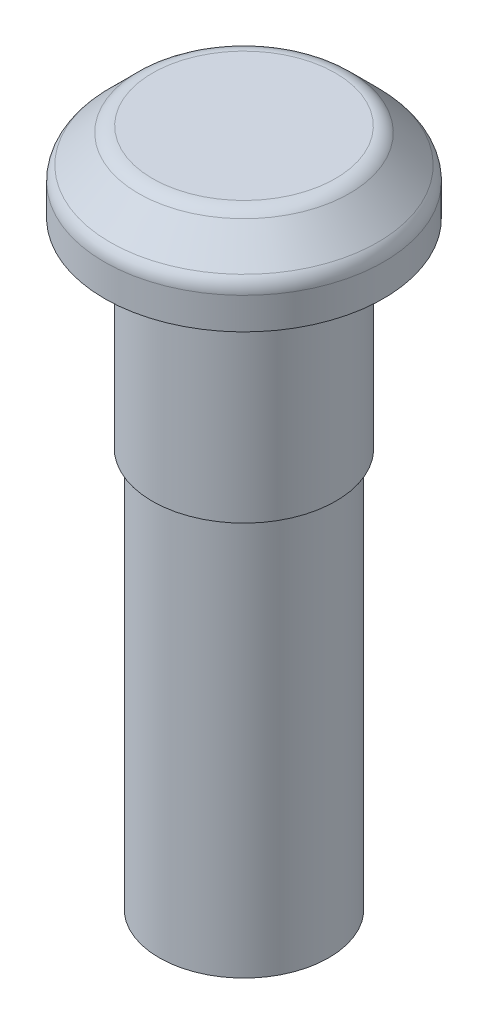
SolidWorks part; units mm, degrees
ref_plane "Front Plane" through (0, 0, 0) normal (0, 0, 1) x (1, 0, 0)
ref_plane "Top Plane" through (0, 0, 0) normal (0, 1, 0) x (1, 0, 0)
ref_plane "Right Plane" through (0, 0, 0) normal (1, 0, 0) x (0, 0, -1)
sketch "Sketch1" plane through (0, 0, 0) normal (0, 1, 0) x (1, 0, 0)
  circle A0 centre (0, 0) radius 2.3
  dimension "D1" = 4.6
extrude "Boss-Extrude1" add sketch "Sketch1" along normal blind 15
sketch "Sketch2" plane through (0, 15, 0) normal (0, 1, 0) x (1, 0, 0)
  circle A0 centre (0, 0) radius 3.5
  dimension "D1" = 7
extrude "Boss-Extrude2" add sketch "Sketch2" along normal blind 2
chamfer "Chamfer1" distance 1 angle 45 1 edges at (0, 17, 3.5)
fillet "Fillet1" radius 0.5 2 edges at (0, 17, 2.5) (0, 16, 3.5)
sketch "Sketch3" plane through (0, 0, 0) normal (0, -1, 0) x (1, 0, 0)
  circle A0 centre (0, 0) radius 2.125
  circle A1 centre (0, 0) radius 2.3
  dimension "D1" = 4.25
  dimension "D2" = 4.6
extrude "Cut-Extrude1" cut sketch "Sketch3" against normal blind 10
